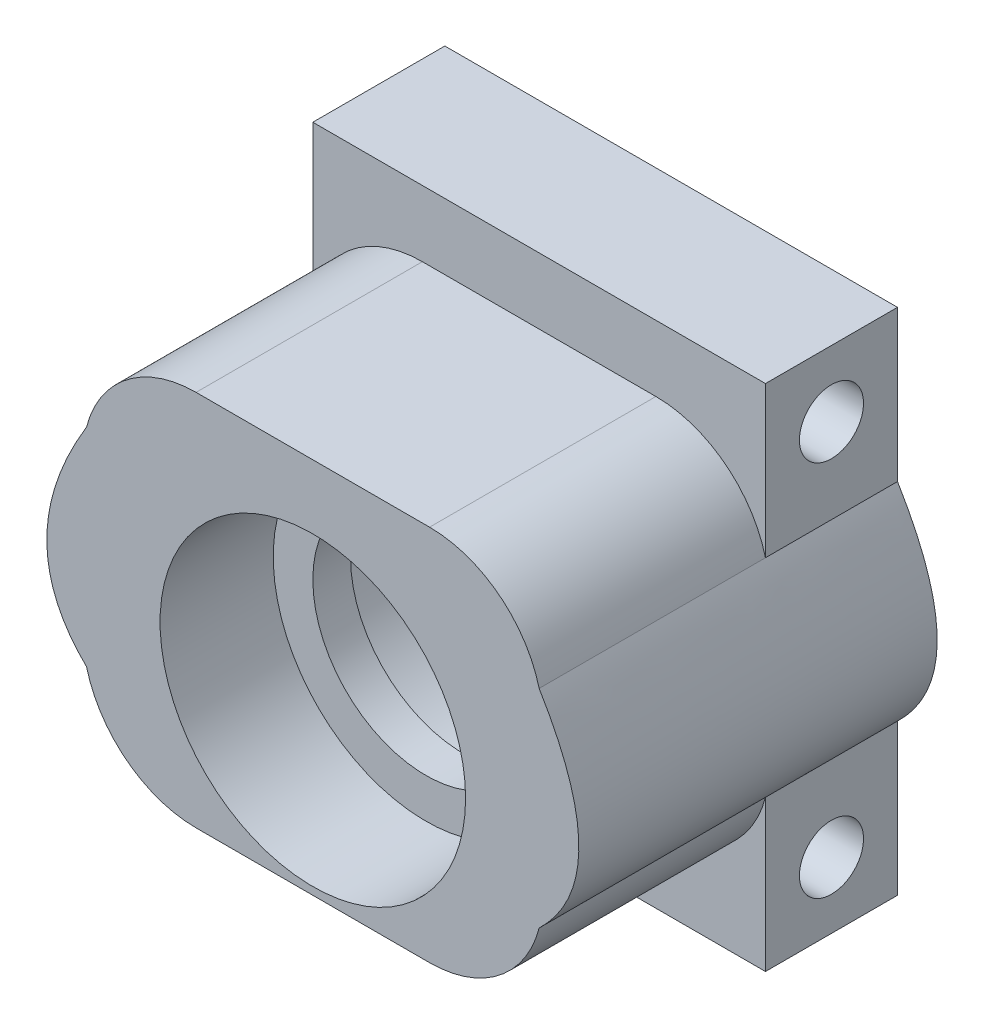
SolidWorks part; units mm, degrees
ref_plane "Front Plane" through (0, 0, 0) normal (0, 0, 1) x (1, 0, 0)
ref_plane "Top Plane" through (0, 0, 0) normal (0, 1, 0) x (1, 0, 0)
ref_plane "Right Plane" through (0, 0, 0) normal (1, 0, 0) x (0, 0, -1)
sketch "Sketch1" plane through (0, 0, 0) normal (0, 0, 1) x (1, 0, 0)
  line L0 (-12, 13.5) -> (-12, 10)
  line L1 (-12, 10) -> (12, 10)
  line L2 (12, 10) -> (12, 13.5)
  line L3 (12, 13.5) -> (-12, 13.5)
  line L4 (-12, -10) -> (-12, -13.5)
  line L5 (-12, -13.5) -> (12, -13.5)
  line L6 (12, -13.5) -> (12, -10)
  line L7 (12, -10) -> (-12, -10)
  line L8 (0, 10.0333) -> (0, -15.702) construction
  line L9 (-12, 10) -> (-12, -10) construction
  line L10 (12, 10) -> (12, -10) construction
  line L11 (12, 10) -> (12, 5.5)
  line L12 (12, -10) -> (12, -5.5)
  line L13 (10, 10) -> (10, 5.5)
  line L14 (10, -10) -> (10, -5.5)
  line L17 (-10, -10) -> (-10, -5.5)
  line L18 (0, 0) -> (14.9553, 0) construction
  line L19 (-12, -10) -> (-12, -5.5)
  line L20 (-12, 10) -> (-12, 5.5)
  line L21 (-10, 10) -> (-10, 5.5)
  circle A0 centre (0, -1.5) radius 8.1
  circle A1 centre (0, -1.5) radius 6
  spline S0 degree 2 poles (12, 5.5) (16.2082, -1.4527) (12, -5.5) knots 0 0 0 0.703674 0.703674 0.703674
  spline S1 degree 2 poles (5.9341, -10) (5.4786, -10.0093) (0, -10) knots 0.968743 0.968743 0.968743 1 1 1
  spline S2 degree 2 poles (10, 5.5) (13.145, -1.5935) (10, -5.5) knots 0 0 0 0.703674 0.703674 0.703674
  spline S3 degree 2 poles (-12, 5.5) (-16.2082, -1.4527) (-12, -5.5) knots 0 0 0 0.703674 0.703674 0.703674
  spline S4 degree 2 poles (-10, 5.5) (-13.145, -1.5935) (-10, -5.5) knots 0 0 0 0.703674 0.703674 0.703674
  point P9 (0, -10)
  point P21 (12, 7.75)
  dimension "D6" = 8
  dimension "D8" = 16.2
  dimension "D9" = 12
  dimension "D10" = 1.5
  dimension "D5" = 8
  dimension "D1" = 3.5
  dimension "D2" = 3.5
  dimension "D3" = 24
  dimension "D4" = 27
  dimension "D7" = 2
extrude "Boss-Extrude1" add sketch "Sketch1" along normal blind 7 contours L2 L3 L0 L1 | S4 L21 L1 L20 S3 L19 L7 L17 | L13 S2 L14 L7 L12 S0 L11 L1 | L7 S1 L4 L5 L6 | L21 S4 L17 L7 L14 S2 L13 L1 A0 region at (0, 11.75, 0) region at (-11.7448, -0.0184, 0) region at (0, 9.6941, 0) region at (11.7448, -0.0184, 0) region at (-0.0008, -11.7504, 0)
extrude "Boss-Extrude2" add sketch "Sketch1<3>" along normal blind 12 from surface contours L21 S4 L17 L7 L14 S2 L13 L1 A0 | S4 L21 L1 L20 S3 L19 L7 L17 | L13 S2 L14 L7 L12 S0 L11 L1 region at (-11.7448, -0.0184, 0) region at (0, 9.6941, 0) region at (11.7448, -0.0184, 0) starting at face at (4.4506, -10, 7)
sketch "Sketch1<3>" plane through (0, 0, 0) normal (0, 0, 1) x (1, 0, 0) same geometry as "Sketch1"
sketch "Sketch2" plane through (-12, 0, 0) normal (-1, 0, 0) x (0, 0, 1)
  line L0 (7, -13.5) -> (0, -13.5) construction
  line L3 (3.5, 10) -> (3.5, -10) construction
  line L4 (7, -10) -> (7, -13.5) construction
  line L5 (0, -13.5) -> (0, -5.5) construction
  point P0 (3.5, 10)
  point P1 (3.5, -10)
  dimension "D1" = 20
  dimension "D2" = 3.5
hole_wizard "M3 Clearance Hole1" positions "Sketch3" profile "Sketch4" hole size "M3" standard "ISO" end condition through all
sketch "Sketch3" plane through (-12, 0, 0) normal (-1, 0, 0) x (0, 0, 1)
  point P0 (3.5, 10)
  point P3 (3.5, -10)
sketch "Sketch4" plane through (-12, 10, 3.5) normal (0, 1, 0) x (0, 0, 1)
  line L0 (0, 0) -> (0, 26.1041)
  line L1 (0, 26.1041) -> (1.7, 26.1041)
  line L2 (1.7, 26.1041) -> (1.7, 0)
  line L5 (1.7, 0) -> (0, 0)
  line L11 (0, -6.35) -> (0, 107.95) construction
  dimension "Thru Hole Dia." = 3.4
  dimension "Thru Hole Depth" = 26.1041
sketch "Sketch5" plane through (0, 13.5, 0) normal (0, 1, 0) x (1, 0, 0)
  line L0 (12, 0) -> (-12, 0) construction
  point P0 (0, -14)
  dimension "D1" = 14
fillet "Fillet1" radius 6 4 edges at (-12, 10, 13) (12, 10, 13) (12, -10, 13) (-12, -10, 13)
extrude "Boss-Extrude3" add sketch "Sketch1<4>" along normal blind 2 from offset 11 contours A0 A1 region at (-7.8709, -1.5, 0)
sketch "Sketch1<4>" plane through (0, 0, 0) normal (0, 0, 1) x (1, 0, 0) same geometry as "Sketch1"
fillet "Fillet2" radius 2 1 edges at (8.1, -1.5, 0)
